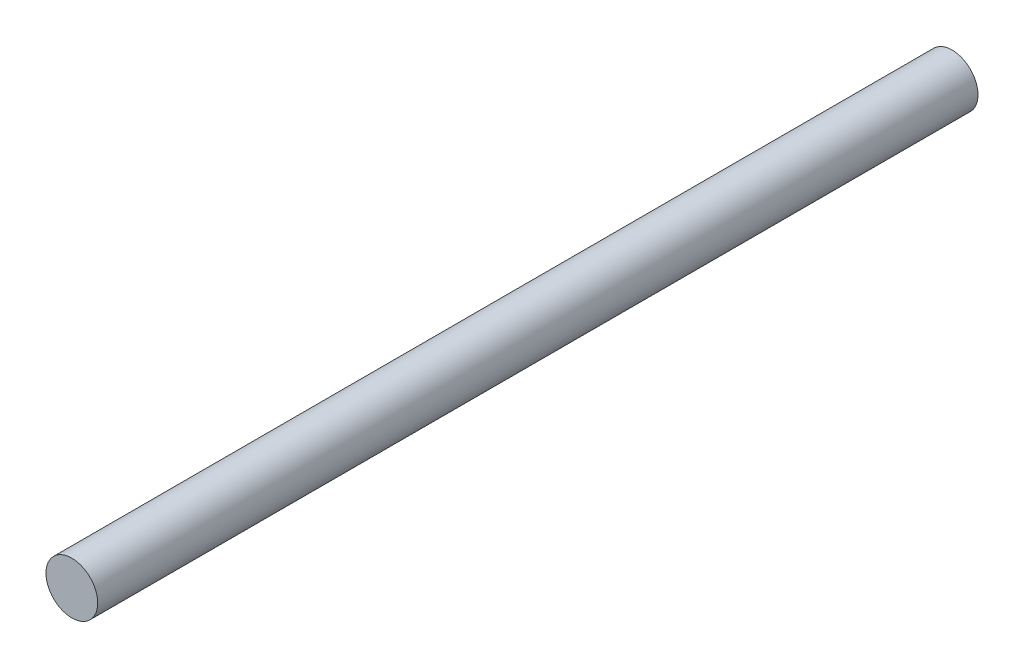
SolidWorks part; units mm, degrees
ref_plane "Front Plane" through (0, 0, 0) normal (0, 0, 1) x (1, 0, 0)
ref_plane "Top Plane" through (0, 0, 0) normal (0, 1, 0) x (1, 0, 0)
ref_plane "Right Plane" through (0, 0, 0) normal (1, 0, 0) x (0, 0, -1)
sketch "Sketch1" plane through (0, 0, 0) normal (0, 0, 1) x (1, 0, 0)
  circle A0 centre (0, 0) radius 1
  dimension "D1" = 2
extrude "Boss-Extrude1" add sketch "Sketch1" along normal blind 34
